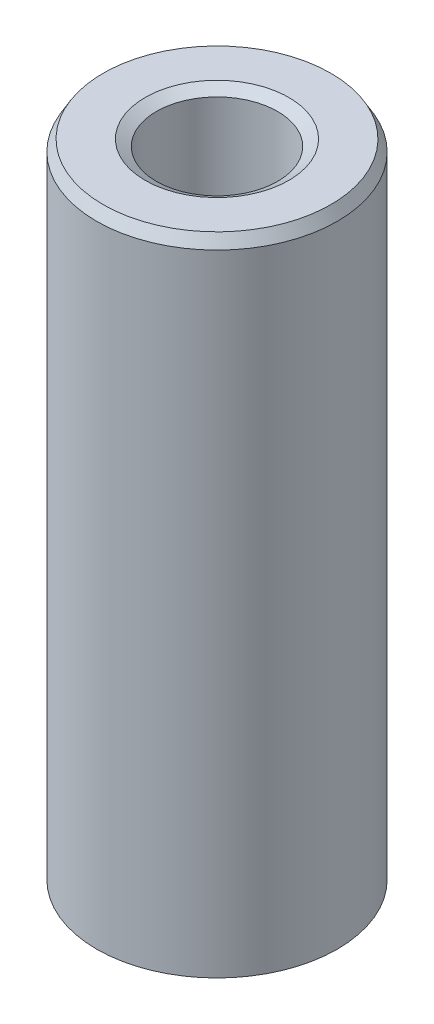
SolidWorks part; units mm, degrees
ref_plane "Front Plane" through (0, 0, 0) normal (0, 0, 1) x (1, 0, 0)
ref_plane "Top Plane" through (0, 0, 0) normal (0, 1, 0) x (1, 0, 0)
ref_plane "Right Plane" through (0, 0, 0) normal (1, 0, 0) x (0, 0, -1)
sketch "Sketch1" plane through (0, 0, 0) normal (0, 1, 0) x (1, 0, 0)
  circle A0 centre (0, 0) radius 10
  dimension "SLEEVE_OD" = 20
extrude "Boss-Extrude1" add sketch "Sketch1" along normal blind 53.8621
sketch "Sketch2" plane through (0, 0, 0) normal (0, 1, 0) x (1, 0, 0)
  circle A0 centre (0, 0) radius 5.0389
  dimension "BORE_D" = 10.0778
extrude "Cut-Extrude1" cut sketch "Sketch2" along normal through all
chamfer "Chamfer1" distance 0.9329 angle 30 4 edges at (0, 53.8621, 5.0389) (0, 0, 5.0389) (0, 0, 10) (0, 53.8621, 10) first distance on face at (0, 53.8621, 5.0389) first distance on face at (0, 0, 5.0389) first distance on face at (0, 53.8621, 10)
